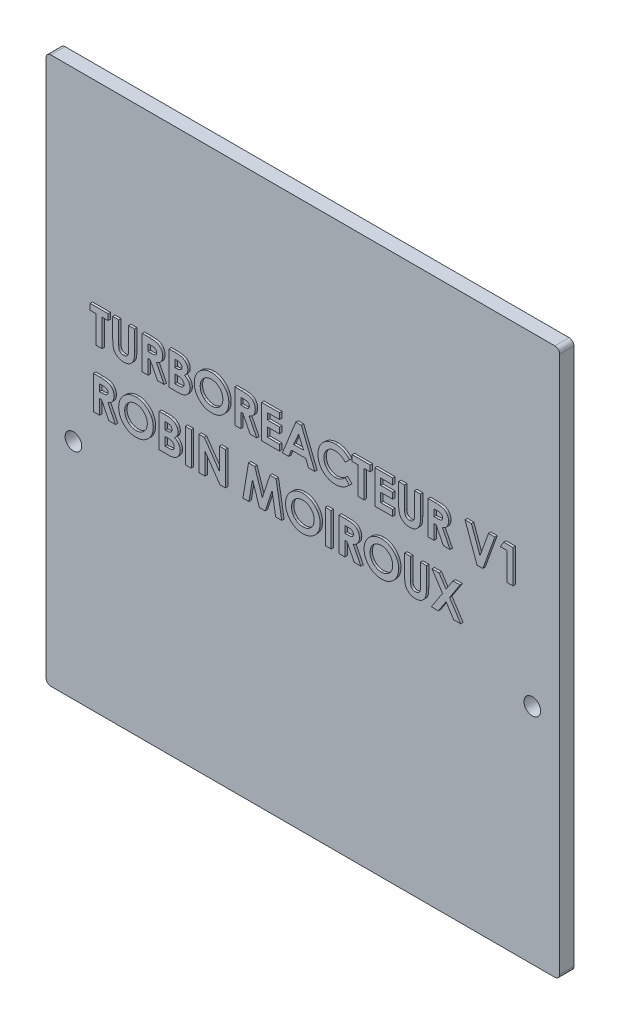
SolidWorks part; units mm, degrees
ref_plane "Plan de face" through (0, 0, 0) normal (0, 0, 1) x (1, 0, 0)
ref_plane "Plan de dessus" through (0, 0, 0) normal (0, 1, 0) x (1, 0, 0)
ref_plane "Plan de droite" through (0, 0, 0) normal (1, 0, 0) x (0, 0, -1)
sketch "Esquisse2" plane through (0, 0, 0) normal (0, 0, 1) x (1, 0, 0)
  line L0 (5.75, 47) -> (102.25, 47) construction
  line L1 (0, 0) -> (108, 0)
  line L2 (0, 0) -> (0, 115)
  line L3 (0, 115) -> (108, 115)
  line L4 (108, 0) -> (108, 115)
  circle A0 centre (5.75, 47) radius 1.75
  circle A1 centre (102.25, 47) radius 1.75
  point P9 (54, 47)
  point P10 (54, 0)
  dimension "D3" = 3.5
  dimension "D4" = 3.5
  dimension "D1" = 115
  dimension "D2" = 108
  dimension "D5" = 96.5
  dimension "D6" = 47
extrude "Boss.-Extru.1" add sketch "Esquisse2" along normal blind 3
fillet "Congé1" radius 1 4 edges at (108, 0, 1.5) (0, 0, 1.5) (0, 115, 1.5) (108, 115, 1.5)
sketch "Esquisse3" plane through (0, 0, 3) normal (0, 0, 1) x (1, 0, 0)
  text T0 "<b>TURBOREACTEUR V1</b>\r\n<b>ROBIN MOIROUX</b>" font "Century Gothic" height 7
extrude "Boss.-Extru.2" add sketch "Esquisse3" along normal blind 0.5
